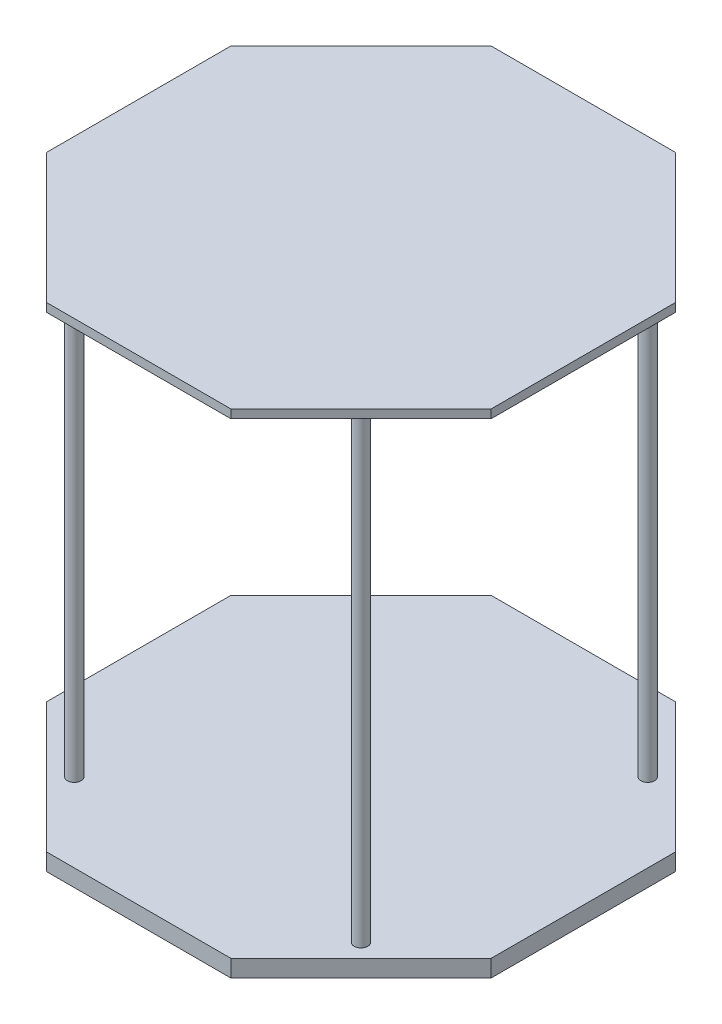
SolidWorks part; units mm, degrees
ref_plane "Front Plane" through (0, 0, 0) normal (0, 0, 1) x (1, 0, 0)
ref_plane "Top Plane" through (0, 0, 0) normal (0, 1, 0) x (1, 0, 0)
ref_plane "Right Plane" through (0, 0, 0) normal (1, 0, 0) x (0, 0, -1)
sketch "Sketch1" plane through (0, 0, 0) normal (0, 1, 0) x (1, 0, 0)
  line L0 (34.249, -82.6844) -> (82.6844, -34.249)
  line L1 (82.6844, 34.249) -> (34.249, 82.6844)
  line L2 (34.249, 82.6844) -> (-34.249, 82.6844)
  line L3 (-34.249, 82.6844) -> (-82.6844, 34.249)
  line L4 (-82.6844, 34.249) -> (-82.6844, -34.249)
  line L5 (-82.6844, -34.249) -> (-34.249, -82.6844)
  line L6 (-34.249, -82.6844) -> (34.249, -82.6844)
  line L7 (82.6844, -34.249) -> (82.6844, 34.249)
  circle A0 centre (0, 0) radius 82.6844 construction
  dimension "D1" = 178.9938
extrude "Boss-Extrude1" add sketch "Sketch1" along normal blind 6.35
sketch "Sketch2" plane through (0, 6.35, 0) normal (0, 1, 0) x (1, 0, 0)
  line L0 (0, -55) -> (0, 55) construction
  line L1 (-55, 0) -> (55, 0) construction
  circle A0 centre (53.34, 53.34) radius 2.54
  circle A1 centre (-53.34, 53.34) radius 2.54
  circle A2 centre (53.34, -53.34) radius 2.54
  circle A3 centre (-53.34, -53.34) radius 2.54
  dimension "D3" = 5.08
  dimension "D1" = 106.68
  dimension "D2" = 106.68
extrude "Boss-Extrude2" add sketch "Sketch2" along normal blind 173.863
sketch "Sketch3" plane through (0, 180.213, 0) normal (0, 1, 0) x (1, 0, 0)
  line L8 (82.6844, -34.249) -> (82.6844, 34.249)
  line L9 (82.6844, 34.249) -> (34.249, 82.6844)
  line L10 (34.249, 82.6844) -> (-34.249, 82.6844)
  line L11 (-34.249, 82.6844) -> (-82.6844, 34.249)
  line L12 (-82.6844, 34.249) -> (-82.6844, -34.249)
  line L13 (-82.6844, -34.249) -> (-34.249, -82.6844)
  line L14 (-34.249, -82.6844) -> (34.249, -82.6844)
  line L15 (34.249, -82.6844) -> (82.6844, -34.249)
  line L16 (82.6844, -34.249) -> (82.6844, 34.249)
  line L17 (82.6844, 34.249) -> (34.249, 82.6844)
  line L18 (34.249, 82.6844) -> (-34.249, 82.6844)
  line L19 (-34.249, 82.6844) -> (-82.6844, 34.249)
  line L20 (-82.6844, 34.249) -> (-82.6844, -34.249)
  line L21 (-82.6844, -34.249) -> (-34.249, -82.6844)
  line L22 (-34.249, -82.6844) -> (34.249, -82.6844)
  line L23 (34.249, -82.6844) -> (82.6844, -34.249)
  dimension "D1" = 0
extrude "Boss-Extrude3" add sketch "Sketch3" along normal blind 3.175
sketch "Sketch4" plane through (0, 0, 0) normal (0, -1, 0) x (1, 0, 0)
  line L0 (0, 0) -> (-74.1328, 42.8006) construction
  line L1 (0, 0) -> (74.1328, 42.8006) construction
  line L2 (0, 0) -> (0, -82.6844) construction
  line L3 (-82.6844, 34.249) -> (-34.249, 82.6844) construction
  line L4 (34.249, 82.6844) -> (82.6844, 34.249) construction
  line L5 (34.249, -82.6844) -> (-34.249, -82.6844) construction
  dimension "D1" = 120
  dimension "D2" = 120
ref_axis "Axis3" through (0, 0, 0) along (0, 0, -1)
ref_axis "Axis4" through (0, 0, 0) along (0.866, 0, 0.5)
ref_axis "Axis5" through (0, 0, 0) along (-0.866, 0, 0.5)
